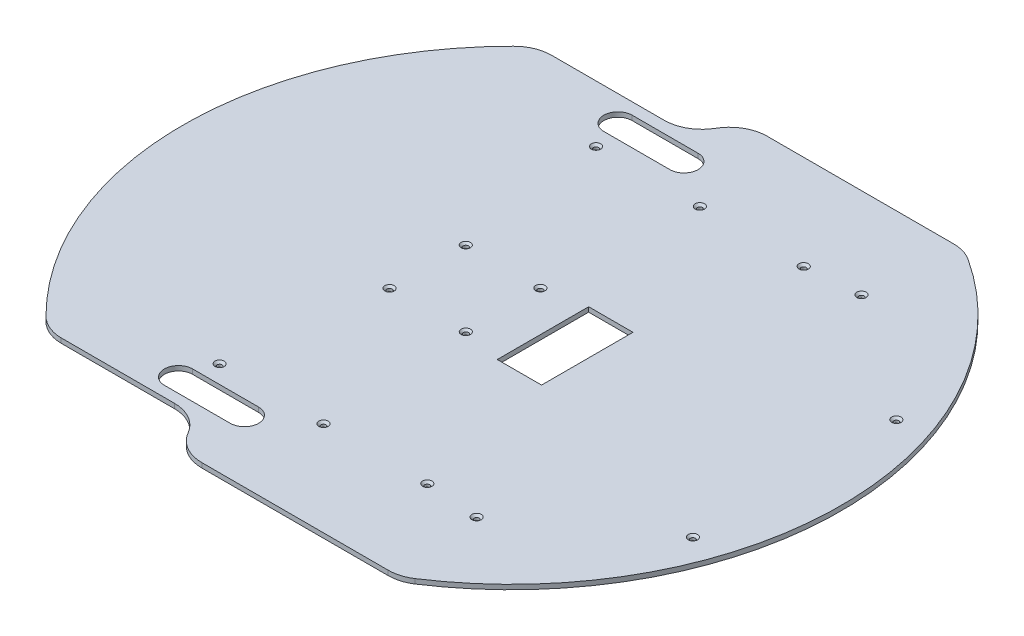
SolidWorks part; units mm, degrees
ref_plane "Plan de face" through (0, 0, 0) normal (0, 0, 1) x (1, 0, 0)
ref_plane "Plan de dessus" through (0, 0, 0) normal (0, 1, 0) x (1, 0, 0)
ref_plane "Plan de droite" through (0, 0, 0) normal (1, 0, 0) x (0, 0, -1)
sketch "Esquisse1" plane through (0, 0, 0) normal (0, 1, 0) x (1, 0, 0)
  line L0 (-138.94, 165.455) -> (-62.65, 165.455)
  line L5 (106.95, -190.145) -> (-18.65, -190.145)
  line L7 (-18.65, 190.855) -> (106.95, 190.855)
  line L8 (-138.94, -164.745) -> (-62.65, -164.745)
  arc A1 (-156.83, 157.725) -> (-138.94, 165.455) centre (-138.5811, 140.0575) cw
  arc A2 (-62.65, 165.455) -> (-40.65, 178.155) centre (-62.647, 190.855) ccw
  arc A3 (-40.65, 178.155) -> (-18.65, 190.855) centre (-18.653, 165.455) cw
  arc A4 (106.95, 190.855) -> (120.78, 186.755) centre (106.9427, 165.455) cw
  arc A5 (120.78, 186.755) -> (120.78, -186.045) centre (-0.716, 0.355) cw
  arc A6 (120.78, -186.045) -> (106.95, -190.145) centre (106.9427, -164.745) cw
  arc A7 (-18.65, -190.145) -> (-40.65, -177.445) centre (-18.653, -164.745) cw
  arc A8 (-40.65, -177.445) -> (-62.65, -164.745) centre (-62.647, -190.145) ccw
  arc A9 (-156.83, -157.015) -> (-138.94, -164.745) centre (-138.5811, -139.3475) ccw
  arc A10 (-156.83, 157.725) -> (-156.83, -157.015) centre (0.4625, 0.355) ccw
  point P0 (0, 0)
  dimension "D3" = 222.5
  dimension "D5" = 25.4
  dimension "D7" = 25.4
  dimension "D9" = 25.4
  dimension "D12" = 25.4
  dimension "D14" = 222.5
  dimension "D15" = 25.4
  dimension "D18" = 25.4
  dimension "D19" = 76.29
  dimension "D21" = 25.4
  dimension "D22" = 25.4
  dimension "D2" = 125.6
  dimension "D4" = 157.725
  dimension "D6" = 76.29
  dimension "D8" = 22
  dimension "D10" = 22
  dimension "D11" = 125.6
  dimension "D13" = 4.1
  dimension "D16" = 4.1
  dimension "D17" = 13.83
  dimension "D20" = 22
  dimension "D23" = 381
  dimension "D24" = 277.61
  dimension "D25" = 330.2
  dimension "D26" = 22
  dimension "D27" = 17.89
  dimension "D28" = 17.89
  dimension "D29" = 7.73
  dimension "D30" = 7.73
  dimension "D31" = 25.4
  dimension "D32" = 156.83
extrude "Boss.-Extru.1" add sketch "Esquisse1" along normal blind 3.18
sketch "Esquisse2" plane through (0, 3.18, 0) normal (0, 1, 0) x (1, 0, 0)
  line L0 (-76.45, -148.105) -> (-32, -148.105) construction
  line L1 (-76.45, -138.575) -> (-32, -138.575)
  line L2 (-76.45, -157.635) -> (-32, -157.635)
  line L3 (-138.94, -164.745) -> (-62.65, -164.745) construction
  line L4 (0, 0) -> (-294.8551, 0) construction
  line L5 (-76.45, 148.105) -> (-32, 148.105) construction
  line L6 (-76.45, 138.575) -> (-32, 138.575)
  line L7 (-76.45, 157.635) -> (-32, 157.635)
  line L8 (20.7, -30.425) -> (50.55, -30.425)
  line L9 (20.7, -30.425) -> (20.7, 31.175)
  line L10 (20.7, 31.175) -> (50.55, 31.175)
  line L11 (50.55, -30.425) -> (50.55, 31.175)
  arc A0 (-76.45, -138.575) -> (-76.45, -157.635) centre (-76.45, -148.105) ccw
  arc A1 (-32, -157.635) -> (-32, -138.575) centre (-32, -148.105) ccw
  arc A2 (-76.45, 138.575) -> (-76.45, 157.635) centre (-76.45, 148.105) cw
  arc A3 (-32, 157.635) -> (-32, 138.575) centre (-32, 148.105) cw
  point P2 (-54.225, -148.105)
  point P15 (-54.225, 148.105)
  dimension "D1" = 9.53
  dimension "D2" = 7.11
  dimension "D3" = 13.8
  dimension "D4" = 44.45
  dimension "D5" = 61.6
  dimension "D6" = 159.64
  dimension "D7" = 134.32
  dimension "D8" = 29.85
extrude "Enlèv. mat.-Extru.1" cut sketch "Esquisse2" against normal blind 3.18
sketch "Esquisse3" plane through (0, 3.18, 0) normal (0, 1, 0) x (1, 0, 0)
  line L1 (0.4625, 0.355) -> (-274.8168, 0.355) construction
  point P0 (-70.35, -126.475)
  point P1 (-0.37, -126.475)
  point P3 (69.61, -126.475)
  point P5 (105.7, -129.345)
  point P8 (190.32, -68.205)
  point P10 (190.32, 68.915)
  point P11 (105.7, 130.055)
  point P12 (69.61, 127.185)
  point P13 (-0.37, 127.185)
  point P14 (-70.35, 127.185)
  dimension "D1" = 12.1
  dimension "D2" = 6.1
  dimension "D3" = 69.98
  dimension "D4" = 69.98
  dimension "D5" = 2.87
  dimension "D6" = 36.09
  dimension "D7" = 84.62
  dimension "D8" = 61.14
hole_wizard "Fraisage pour vis à tête fraisée M31" positions "Esquisse3D2" profile "Esquisse8" countersink size "M3" standard "Ansi Metric" end condition through all
sketch3d "Esquisse3D2"
  point P0 (-70.35, 3.18, 126.475)
  point P3 (-0.37, 3.18, 126.475)
  point P6 (69.61, 3.18, 126.475)
  point P9 (105.7, 3.18, 129.345)
  point P12 (190.32, 3.18, 68.205)
  point P15 (190.32, 3.18, -68.915)
  point P18 (105.7, 3.18, -130.055)
  point P21 (69.61, 3.18, -127.185)
  point P24 (-0.37, 3.18, -127.185)
  point P27 (-70.35, 3.18, -127.185)
sketch "Esquisse8" plane through (-70.35, 3.18, 126.475) normal (1, 0, 0) x (0, 0, 1)
  line L0 (0, 0) -> (0, 3.18)
  line L1 (0, 3.18) -> (1.7, 3.18)
  line L2 (1.7, 3.18) -> (1.7, 1.45)
  line L3 (1.7, 1.45) -> (3.15, 0)
  line L5 (3.15, 0) -> (0, 0)
  line L6 (-1.7, 1.45) -> (-3.15, 0) construction
  line L11 (0, -6.35) -> (0, 107.95) construction
  dimension "Diamètre du perçage jusqu'au prochain" = 3.4
  dimension "Profondeur du perçage jusqu'au prochain" = 3.18
  dimension "Diamètre du fraisage entrant" = 6.3
  dimension "Angle du fraisage entrant" = 90
sketch "Esquisse9" plane through (0, 3.18, 0) normal (0, 1, 0) x (1, 0, 0)
  line L0 (20.7, 31.175) -> (20.7, -30.425) construction
  line L1 (-151.0308, 0.355) -> (43.8249, -112.145) construction
  line L2 (43.8249, -112.145) -> (43.8249, 112.855) construction
  line L3 (43.8249, 112.855) -> (-151.0308, 0.355) construction
  line L13 (-4.72, 27.445) -> (-4.72, -26.555) construction
  line L14 (-4.72, -26.555) -> (-59.23, -26.5244) construction
  line L15 (-59.23, -26.5244) -> (-58.3786, 27.829) construction
  line L16 (-58.3786, 27.829) -> (-4.72, 27.445) construction
  line L17 (0.4625, 0.355) -> (-274.8168, 0.355) construction
  circle A0 centre (-21.127, 0.355) radius 64.9519 construction
  dimension "D2" = 54.36
  dimension "D1" = 225
  dimension "D3" = 54
  dimension "D4" = 3.73
  dimension "D5" = 25.42
  dimension "D6" = 53.66
  dimension "D7" = 54.51
  dimension "D8" = 90.41
  dimension "D9" = 90.487
  dimension "D10" = 21.13
  dimension "D11" = 0
sketch "Esquisse11" plane through (0, 3.18, 0) normal (0, 1, 0) x (1, 0, 0)
  line L0 (-56.6966, 25.755) -> (-6.0543, -24.8462) construction
  line L1 (-58.3873, 27.46) -> (-4.7273, 27.46) construction
  line L2 (-58.3873, 27.46) -> (-58.8471, -26.8981) construction
  line L3 (-58.8471, -26.8981) -> (-4.3371, -26.54) construction
  line L4 (-4.7273, 27.46) -> (-4.3371, -26.54) construction
  circle A0 centre (-56.6966, 25.755) radius 1.705 construction
  circle A1 centre (-6.0543, -24.8462) radius 1.705 construction
  circle A2 centre (-57.1275, -25.1817) radius 1.705 construction
  circle A3 centre (-6.42, 25.755) radius 1.705 construction
  dimension "D5" = 3.41
  dimension "D6" = 54.51
  dimension "D1" = 54.36
  dimension "D2" = 71.59
  dimension "D3" = 53.66
  dimension "D4" = 54
  dimension "D7" = 27.12
  dimension "D8" = 5.42
hole_wizard "Fraisage pour vis à tête fraisée M33" positions "Esquisse3D4" profile "Esquisse12" countersink size "M3" standard "Ansi Metric" end condition through all
sketch3d "Esquisse3D4"
  point P0 (-56.6966, 3.18, -25.755)
  point P3 (-6.42, 3.18, -25.755)
  point P6 (-6.0543, 3.18, 24.8462)
  point P9 (-57.1275, 3.18, 25.1817)
sketch "Esquisse12" plane through (-56.6966, 3.18, -25.755) normal (1, 0, 0) x (0, 0, 1)
  line L0 (0, 0) -> (0, 3.18)
  line L1 (0, 3.18) -> (1.8, 3.18)
  line L2 (1.8, 3.18) -> (1.8, 1.35)
  line L3 (1.8, 1.35) -> (3.15, 0)
  line L5 (3.15, 0) -> (0, 0)
  line L6 (-1.8, 1.35) -> (-3.15, 0) construction
  line L11 (0, -6.35) -> (0, 107.95) construction
  dimension "Diamètre du perçage jusqu'au prochain" = 3.6
  dimension "Profondeur du perçage jusqu'au prochain" = 3.18
  dimension "Diamètre du fraisage entrant" = 6.3
  dimension "Angle du fraisage entrant" = 90
sketch "Esquisse13" plane through (0, 3.18, 3.18) normal (0, 1, 0) x (1, 0, 0)
  line L70 (26.0521, -121.803) -> (52.0329, -106.803) construction
  line L71 (-152.6575, 25.695) -> (-151.0175, 25.695) construction
  line L72 (-152.6575, 25.695) -> (-152.6575, -4.305) construction
  line L73 (-152.6575, -4.305) -> (-151.0175, -4.305) construction
  line L74 (-151.0175, 25.695) -> (-151.0175, -4.305) construction
  line L75 (44.2282, -108.965) -> (44.2282, 116.035) construction
  line L76 (44.2282, 116.035) -> (-150.6275, 3.535) construction
  line L77 (-150.6275, 3.535) -> (44.2282, -108.965) construction
  line L82 (52.0329, -106.803) -> (51.2129, -105.3827) construction
  line L83 (51.2129, -105.3827) -> (25.2321, -120.3827) construction
  line L84 (25.2321, -120.3827) -> (26.0521, -121.803) construction
  line L85 (37.6336, 120.2927) -> (63.6144, 105.2927) construction
  line L86 (63.6144, 105.2927) -> (64.4344, 106.713) construction
  line L87 (64.4344, 106.713) -> (38.4536, 121.713) construction
  line L88 (38.4536, 121.713) -> (37.6336, 120.2927) construction
  line L92 (0.4625, 3.535) -> (-274.8168, 3.535) construction
  circle A4 centre (-150.6275, 3.535) radius 5 construction
  circle A5 centre (44.2282, 116.035) radius 5 construction
  circle A6 centre (44.2282, -108.965) radius 5 construction
  circle A11 centre (-20.7237, 3.535) radius 64.9519 construction
  circle A12 centre (69.61, 130.365) radius 3.15 construction
  circle A13 centre (105.7, 133.235) radius 3.15 construction
  circle A14 centre (69.61, -123.295) radius 3.15 construction
  circle A15 centre (105.7, -126.165) radius 3.15 construction
  dimension "D9" = 25.3818
  dimension "D12" = 0.39
  dimension "D13" = 1.64
  dimension "D14" = 0.39
  dimension "D33" = 7.84
  dimension "D34" = 225
  dimension "D3" = 60
  dimension "D4" = 60
  dimension "D5" = 60
  dimension "D6" = 93.5
  dimension "D7" = 25.3818
  dimension "D8" = 14.33
  dimension "D10" = 14.33
  dimension "D11" = 7.84
  dimension "D15" = 0.39
  dimension "D16" = 0
  dimension "D17" = 0
  dimension "D18" = 36.09
  dimension "D19" = 2.87
  dimension "D20" = 1.64
  dimension "D21" = 7.84
  dimension "D23" = 1.64
  dimension "D24" = 30
  dimension "D25" = 30
  dimension "D29" = 60
  dimension "D30" = 30
  dimension "D35" = 60
